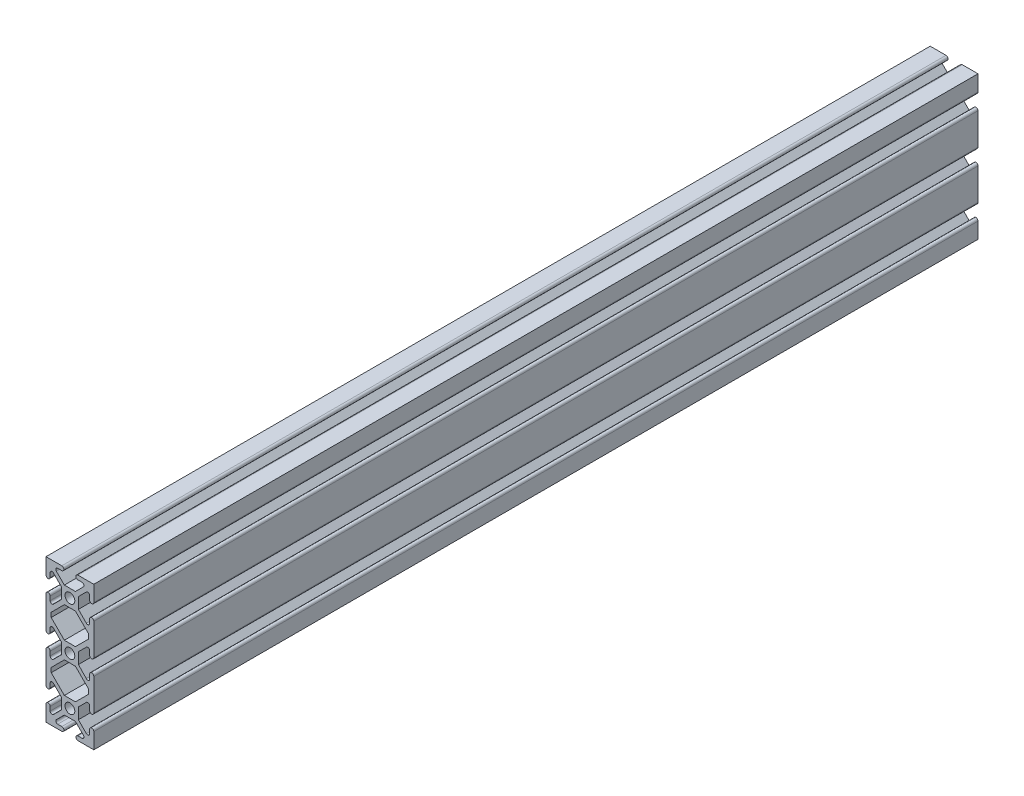
SolidWorks part; units mm, degrees
ref_plane "Front Plane" through (0, 0, 0) normal (0, 0, 1) x (1, 0, 0)
ref_plane "Top Plane" through (0, 0, 0) normal (0, 1, 0) x (1, 0, 0)
ref_plane "Right Plane" through (0, 0, 0) normal (1, 0, 0) x (0, 0, -1)
sketch "Sketch1" plane through (0, 0, 0) normal (0, 0, 1) x (1, 0, 0)
  line L0 (-8.7558, -7.1932) -> (-4.5085, -2.9459)
  line L1 (-9.9314, 13.906) -> (-9.9314, 11.494)
  line L2 (-9.9314, 13.906) -> (-2.9459, 20.8915)
  line L3 (2.9459, 4.5085) -> (9.9314, 11.494)
  line L4 (-4.5085, 2.9459) -> (-4.5085, -2.9459)
  line L5 (-4.5085, 2.9459) -> (-8.7558, 7.1932)
  line L6 (8.7558, 7.1932) -> (4.5085, 2.9459)
  line L7 (4.5085, -2.9459) -> (4.5085, 2.9459)
  line L8 (-9.9314, -11.494) -> (-9.9314, -13.906)
  line L9 (-7.1932, -34.1558) -> (-2.9459, -29.9085)
  line L10 (2.9459, -29.9085) -> (-2.9459, -29.9085)
  line L11 (-8.7558, -32.5932) -> (-4.5085, -28.3459)
  line L12 (-9.9314, -11.494) -> (-2.9459, -4.5085)
  line L13 (8.7558, -32.5932) -> (4.5085, -28.3459)
  line L14 (2.9459, -29.9085) -> (7.1932, -34.1558)
  line L15 (-4.5085, -22.4541) -> (-4.5085, -28.3459)
  line L16 (-12.7, 21.0977) -> (-12.7, 4.3023)
  line L17 (-12.7, -4.3023) -> (-12.7, -21.0977)
  line L18 (-12.7, 29.7023) -> (-12.7, 38.1)
  line L19 (-10.4902, 29.7023) -> (-10.4902, 31.8748)
  line L23 (-10.4902, 18.9252) -> (-10.4902, 21.0977)
  line L24 (-12.7, 38.1) -> (-4.3023, 38.1)
  line L25 (4.3023, 38.1) -> (12.7, 38.1)
  line L26 (12.7, 38.1) -> (12.7, 29.7023)
  line L27 (12.7, 21.0977) -> (12.7, 4.3023)
  line L28 (12.7, -4.3023) -> (12.7, -21.0977)
  line L29 (-10.4902, 4.3023) -> (-10.4902, 6.4748)
  line L33 (-10.4902, -6.4748) -> (-10.4902, -4.3023)
  line L34 (-12.7, -29.7023) -> (-12.7, -38.1)
  line L35 (-12.7, -38.1) -> (-4.3023, -38.1)
  line L36 (4.3023, -38.1) -> (12.7, -38.1)
  line L37 (12.7, -38.1) -> (12.7, -29.7023)
  line L38 (-4.5085, -22.4541) -> (-8.7558, -18.2068)
  line L39 (-10.4902, -21.0977) -> (-10.4902, -18.9252)
  line L43 (-10.4902, -31.8748) -> (-10.4902, -29.7023)
  line L44 (4.5085, -22.4541) -> (4.5085, -28.3459)
  line L45 (4.5085, -22.4541) -> (8.7558, -18.2068)
  line L46 (2.9459, -20.8915) -> (-2.9459, -20.8915)
  line L47 (-2.9459, -20.8915) -> (-9.9314, -13.906)
  line L48 (-4.3023, -35.8902) -> (-6.4748, -35.8902)
  line L52 (6.4748, -35.8902) -> (4.3023, -35.8902)
  line L53 (2.9459, -4.5085) -> (-2.9459, -4.5085)
  line L54 (2.9459, -4.5085) -> (9.9314, -11.494)
  line L55 (9.9314, -11.494) -> (9.9314, -13.906)
  line L56 (9.9314, -13.906) -> (2.9459, -20.8915)
  line L57 (10.4902, -29.7023) -> (10.4902, -31.8748)
  line L61 (10.4902, -18.9252) -> (10.4902, -21.0977)
  line L62 (4.5085, -2.9459) -> (8.6807, -7.267)
  line L63 (2.9459, 4.5085) -> (-2.9459, 4.5085)
  line L64 (-2.9459, 4.5085) -> (-9.9314, 11.494)
  line L65 (9.9314, 13.906) -> (9.9314, 11.494)
  line L66 (2.9459, 20.8915) -> (-2.9459, 20.8915)
  line L67 (10.4902, -4.3023) -> (10.4902, -6.4748)
  line L71 (10.4902, 6.4748) -> (10.4902, 4.3023)
  line L72 (2.9459, 20.8915) -> (9.9314, 13.906)
  line L73 (-8.7558, 32.5932) -> (-4.5085, 28.3459)
  line L74 (-7.1932, 34.1558) -> (-2.9459, 29.9085)
  line L75 (8.7558, 18.2068) -> (4.5085, 22.4541)
  line L76 (-4.5085, 22.4541) -> (-4.5085, 28.3459)
  line L77 (10.4902, 21.0977) -> (10.4902, 18.9252)
  line L81 (10.4902, 31.8748) -> (10.4902, 29.7023)
  line L82 (-4.5085, 22.4541) -> (-8.7558, 18.2068)
  line L83 (2.9459, 29.9085) -> (-2.9459, 29.9085)
  line L84 (2.9459, 29.9085) -> (7.1932, 34.1558)
  line L85 (4.5085, 28.3459) -> (4.5085, 22.4541)
  line L86 (4.3023, 35.8902) -> (6.4748, 35.8902)
  line L90 (-6.4748, 35.8902) -> (-4.3023, 35.8902)
  line L91 (4.5085, 28.3459) -> (8.7558, 32.5932)
  circle A0 centre (0, 25.4) radius 2.6035
  arc A5 (10.4902, -6.4748) -> (8.6807, -7.267) centre (9.4899, -6.6526) cw
  circle A17 centre (0, -25.4) radius 2.6035
  circle A18 centre (0, 0) radius 2.6035
  arc A24 (-12.7, 29.7023) -> (-10.4902, 29.7023) centre (-11.5951, 29.7023) ccw
  arc A25 (-10.4902, 31.8748) -> (-8.7558, 32.5932) centre (-9.4742, 31.8748) cw
  arc A28 (-8.7558, 18.2068) -> (-10.4902, 18.9252) centre (-9.4742, 18.9252) cw
  arc A29 (-10.4902, 21.0977) -> (-12.7, 21.0977) centre (-11.5951, 21.0977) ccw
  arc A34 (-12.7, 4.3023) -> (-10.4902, 4.3023) centre (-11.5951, 4.3023) ccw
  arc A35 (-10.4902, 6.4748) -> (-8.7558, 7.1932) centre (-9.4742, 6.4748) cw
  arc A38 (-8.7558, -7.1932) -> (-10.4902, -6.4748) centre (-9.4742, -6.4748) cw
  arc A39 (-10.4902, -4.3023) -> (-12.7, -4.3023) centre (-11.5951, -4.3023) ccw
  arc A44 (-12.7, -21.0977) -> (-10.4902, -21.0977) centre (-11.5951, -21.0977) ccw
  arc A45 (-10.4902, -18.9252) -> (-8.7558, -18.2068) centre (-9.4742, -18.9252) cw
  arc A48 (-8.7558, -32.5932) -> (-10.4902, -31.8748) centre (-9.4742, -31.8748) cw
  arc A49 (-10.4902, -29.7023) -> (-12.7, -29.7023) centre (-11.5951, -29.7023) ccw
  arc A55 (-4.3023, -38.1) -> (-4.3023, -35.8902) centre (-4.3023, -36.9951) ccw
  arc A56 (-6.4748, -35.8902) -> (-7.1932, -34.1558) centre (-6.4748, -34.8742) cw
  arc A59 (7.1932, -34.1558) -> (6.4748, -35.8902) centre (6.4748, -34.8742) cw
  arc A60 (4.3023, -35.8902) -> (4.3023, -38.1) centre (4.3023, -36.9951) ccw
  arc A66 (12.7, -29.7023) -> (10.4902, -29.7023) centre (11.5951, -29.7023) ccw
  arc A67 (10.4902, -31.8748) -> (8.7558, -32.5932) centre (9.4742, -31.8748) cw
  arc A70 (8.7558, -18.2068) -> (10.4902, -18.9252) centre (9.4742, -18.9252) cw
  arc A71 (10.4902, -21.0977) -> (12.7, -21.0977) centre (11.5951, -21.0977) ccw
  arc A76 (12.7, -4.3023) -> (10.4902, -4.3023) centre (11.5951, -4.3023) ccw
  arc A80 (8.7558, 7.1932) -> (10.4902, 6.4748) centre (9.4742, 6.4748) cw
  arc A81 (10.4902, 4.3023) -> (12.7, 4.3023) centre (11.5951, 4.3023) ccw
  arc A86 (12.7, 21.0977) -> (10.4902, 21.0977) centre (11.5951, 21.0977) ccw
  arc A87 (10.4902, 18.9252) -> (8.7558, 18.2068) centre (9.4742, 18.9252) cw
  arc A90 (8.7558, 32.5932) -> (10.4902, 31.8748) centre (9.4742, 31.8748) cw
  arc A91 (10.4902, 29.7023) -> (12.7, 29.7023) centre (11.5951, 29.7023) ccw
  arc A97 (4.3023, 38.1) -> (4.3023, 35.8902) centre (4.3023, 36.9951) ccw
  arc A98 (6.4748, 35.8902) -> (7.1932, 34.1558) centre (6.4748, 34.8742) cw
  arc A101 (-7.1932, 34.1558) -> (-6.4748, 35.8902) centre (-6.4748, 34.8742) cw
  arc A102 (-4.3023, 35.8902) -> (-4.3023, 38.1) centre (-4.3023, 36.9951) ccw
  point P6 (-9.9314, 12.7)
  point P10 (9.9314, 12.7)
  point P12 (0, 20.8915)
  point P18 (-4.5085, 0)
  point P21 (4.5085, 0)
  point P25 (0, 4.5085)
  point P28 (-4.5085, 0)
  point P29 (4.5085, 0)
  point P34 (0, -29.9085)
  point P39 (-9.9314, -12.7)
  point P40 (-4.5085, -25.4)
  point P42 (4.5085, -25.4)
  point P44 (0, -20.8915)
  point P47 (0, -4.5085)
  point P54 (0, -20.8915)
  point P59 (-9.9314, -12.7)
  point P60 (9.9314, -12.7)
  point P61 (-4.5085, -25.4)
  point P62 (4.5085, -25.4)
  point P63 (0, -29.9085)
  point P64 (0, -4.5085)
  point P65 (0, 4.5085)
  point P66 (-9.9314, 12.7)
  point P73 (-4.5085, 25.4)
  point P75 (0, 29.9085)
  point P77 (4.5085, 25.4)
  point P85 (0, 20.8915)
  point P86 (9.9314, 12.7)
  point P87 (-4.5085, 25.4)
  point P88 (4.5085, 25.4)
  point P89 (0, 29.9085)
extrude "Boss-Extrude1" add sketch "Sketch1" against normal blind 469.9
